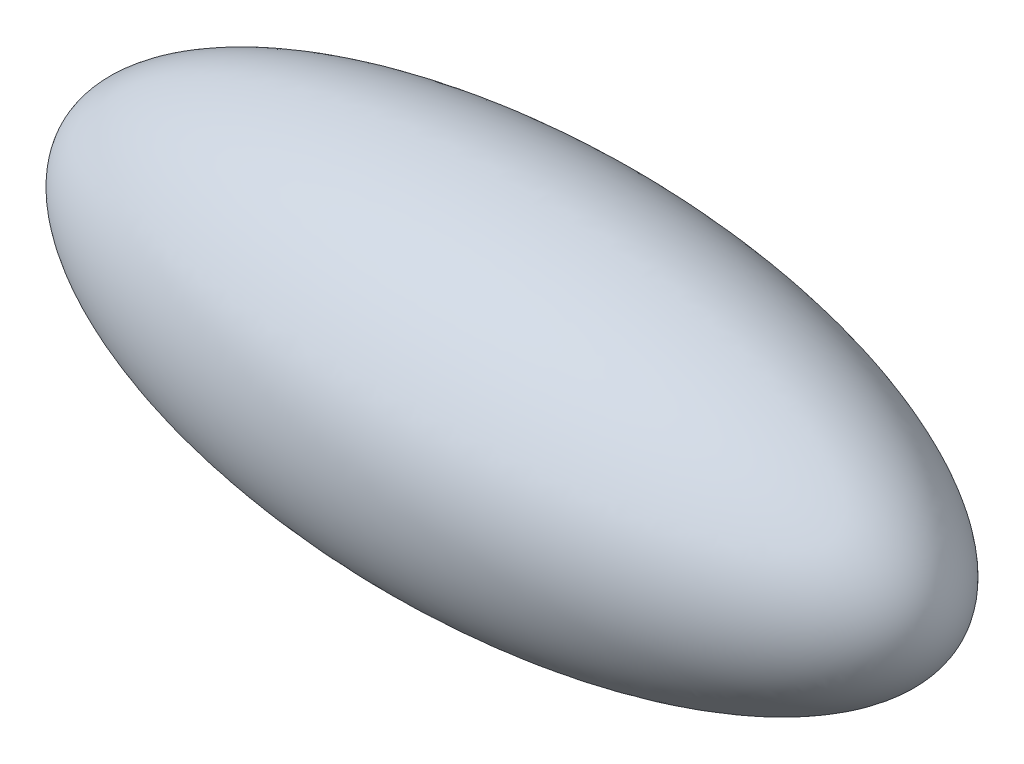
SolidWorks part; units mm, degrees
ref_plane "Front Plane" through (0, 0, 0) normal (0, 0, 1) x (1, 0, 0)
ref_plane "Top Plane" through (0, 0, 0) normal (0, 1, 0) x (1, 0, 0)
ref_plane "Right Plane" through (0, 0, 0) normal (1, 0, 0) x (0, 0, -1)
sketch "Sketch2" plane through (0, 0, 0) normal (0, 1, 0) x (1, 0, 0)
  line L0 (-0.5, 0) -> (0.5, 0) construction
  ellipse E0 centre (0, 0) end of major axis (-0.5, 0) minor radius 0.2
revolve "Revolve2" add sketch "Sketch2" angle 360 about L0 region at (0, 0, 0.0849)
